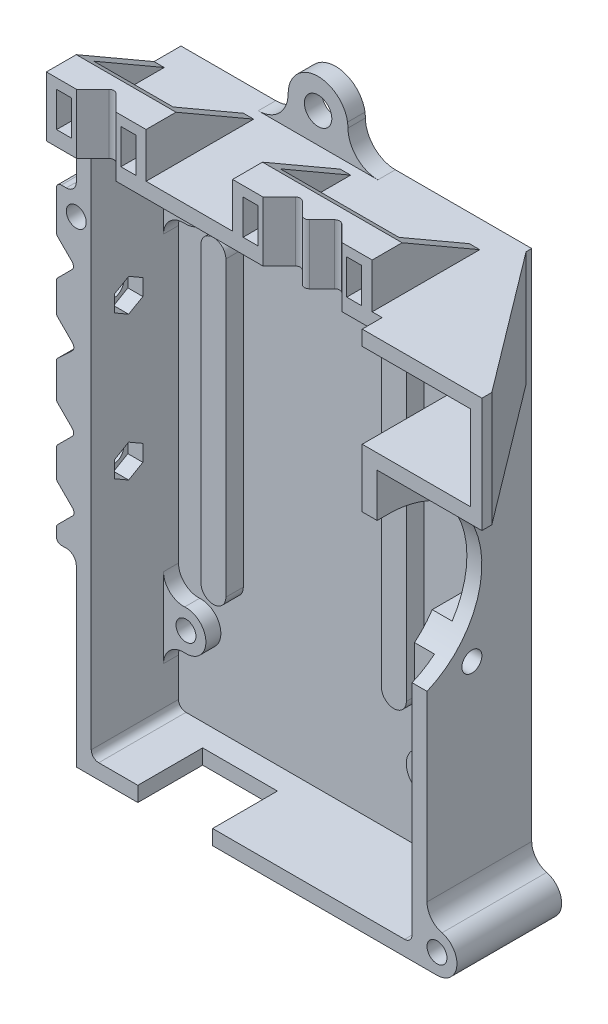
SolidWorks part; units mm, degrees
note: The reader was unsure of these and kept them because the rebuilt part matched: shared geometry of "Sketch6<4>", "Sketch11<3>", "Sketch11<4>".
ref_plane "Front Plane" through (0, 0, 0) normal (0, 0, 1) x (1, 0, 0)
ref_plane "Top Plane" through (0, 0, 0) normal (0, 1, 0) x (1, 0, 0)
ref_plane "Right Plane" through (0, 0, 0) normal (1, 0, 0) x (0, 0, -1)
sketch "Sketch6" plane through (0, 0, 0) normal (0, 0, 1) x (1, 0, 0)
  line L0 (4, 12) -> (4, 126.75)
  line L1 (4, 69.375) -> (74.35, 69.375) construction
  line L2 (74.35, 126.75) -> (4, 126.75)
  line L3 (23, 12) -> (47.3, 12)
  line L4 (74.35, 23.746) -> (74.35, 126.75)
  line L5 (71.35, 123.75) -> (7, 123.75)
  line L6 (69.85, 15) -> (8.5, 15)
  line L7 (71.35, 123.75) -> (71.35, 16.5)
  line L8 (76.35, 12) -> (47.3, 12)
  line L9 (7, 16.5) -> (7, 123.75)
  line L10 (23, 12) -> (4, 12)
  arc A3 (74.35, 23.746) -> (77.35, 19.873) centre (78.35, 23.746) ccw
  arc A4 (77.35, 19.873) -> (76.35, 12) centre (76.35, 16) cw
  arc A5 (23, 12) -> (29, 6) centre (23, 6) cw
  arc A6 (47.3, 12) -> (41, 5.998) centre (47.0109, 5.996) ccw
  arc A7 (41, 5.998) -> (29, 6) centre (35, 6) cw
  arc A8 (7, 16.5) -> (8.5, 15) centre (8.5, 16.5) ccw
  arc A9 (69.85, 15) -> (71.35, 16.5) centre (69.85, 16.5) ccw
  point P31 (0, 0)
  dimension "D1" = 4
  dimension "D2" = 4
  dimension "D3" = 6
  dimension "D4" = 6.0109
  dimension "D5" = 1.5
  dimension "D6" = 4
  dimension "D7" = 7
  dimension "D8" = 29
  dimension "D9" = 47.3
  dimension "D10" = 74.35
  dimension "D11" = 76.35
  dimension "D12" = 5.996
  dimension "D13" = 71.35
  dimension "D16" = 15
  dimension "D20" = 123.75
  dimension "D21" = 126.75
extrude "Boss-Extrude1" add sketch "Sketch6" along normal blind 21
extrude "Boss-Extrude2" add sketch "Sketch6<4>" along normal blind 3.5
sketch "Sketch6<4>" plane through (0, 0, 0) normal (0, 0, 1) x (1, 0, 0) same geometry as "Sketch6"
sketch "Sketch9" plane through (0, 0, 0) normal (0, 0, 1) x (1, 0, 0)
  line L0 (4, 12) -> (4, 126.75) construction
  line L1 (1, 111.5979) -> (2, 111.5979)
  line L2 (0, 103.0122) -> (0, 110.5979)
  line L3 (3.1815, 99.3365) -> (0.1809, 102.3372)
  line L4 (0, 89.1126) -> (0, 94.2842)
  line L5 (0.1809, 95.0234) -> (3.1815, 98.024)
  line L6 (0.1809, 88.3736) -> (3.1815, 85.373)
  line L7 (0.1809, 81.0599) -> (3.1815, 83.8996)
  line L8 (0, 74.2132) -> (0, 80.3848)
  line L9 (0.1809, 73.449) -> (3.1815, 70.4484)
  line L10 (4, 47) -> (4, 113.5979)
  line L11 (3.1815, 69.0344) -> (0.2832, 66.136)
  line L12 (0, 65.4853) -> (0, 60.3137)
  line L13 (3.1815, 56.7082) -> (0.2832, 59.6066)
  line L14 (3.1815, 55.1815) -> (0.2859, 52.2858)
  line L15 (0, 50) -> (0, 51.5858)
  line L16 (1, 49) -> (2, 49)
  line L18 (4, 12) -> (4, 47) construction
  arc A0 (4, 113.5979) -> (2, 111.5979) centre (2, 113.5979) cw
  arc A1 (1, 111.5979) -> (0, 110.5979) centre (1, 110.5979) ccw
  arc A2 (3.1815, 99.3365) -> (3.1815, 98.024) centre (2.427, 98.6803) cw
  arc A3 (0, 103.0122) -> (0.1809, 102.3372) centre (0.9955, 102.9172) ccw
  arc A4 (0, 94.2842) -> (0.1809, 95.0234) centre (0.9887, 94.4339) cw
  arc A5 (0, 89.1126) -> (0.1809, 88.3736) centre (0.9887, 88.963) ccw
  arc A6 (3.1815, 85.373) -> (3.1815, 83.8996) centre (2.5053, 84.6363) cw
  arc A7 (0, 80.3848) -> (0.1809, 81.0599) centre (0.9955, 80.4798) cw
  arc A8 (0, 74.2132) -> (0.1809, 73.449) centre (0.9854, 74.043) ccw
  arc A9 (3.1815, 69.0344) -> (3.1815, 70.4484) centre (2.4743, 69.7414) ccw
  arc A10 (0.2832, 66.136) -> (0, 65.4853) centre (0.9989, 65.4376) ccw
  arc A11 (0, 60.3137) -> (0.2832, 59.6066) centre (1, 60.3039) ccw
  arc A12 (3.1815, 56.7082) -> (3.1815, 55.1815) centre (2.5356, 55.9449) cw
  arc A13 (0.2859, 52.2858) -> (0, 51.5858) centre (1, 51.5858) ccw
  arc A14 (0, 50) -> (1, 49) centre (1, 50) ccw
  arc A15 (2, 49) -> (4, 47) centre (2, 47) cw
  point P1 (3.5356, 55.9449)
  point P39 (3.4743, 69.7414)
  point P57 (3.5053, 84.6363)
  point P58 (0, 0)
  point P60 (3.427, 98.6803)
  dimension "D1" = 2
  dimension "D2" = 1
  dimension "D3" = 1
  dimension "D4" = 1
  dimension "D5" = 1
  dimension "D6" = 1
  dimension "D7" = 1
  dimension "D8" = 1
  dimension "D9" = 1
  dimension "D10" = 1
  dimension "D11" = 1
  dimension "D12" = 1
  dimension "D13" = 1
  dimension "D14" = 1
  dimension "D15" = 1
  dimension "D16" = 2
  dimension "D17" = 1.5858
  dimension "D18" = 1
  dimension "D19" = 5.1716
  dimension "D20" = 7.3137
  dimension "D21" = 6.1716
  dimension "D22" = 7.3137
  dimension "D23" = 5.1716
  dimension "D24" = 7.3138
  dimension "D25" = 7.5858
  dimension "D26" = 1
  dimension "D27" = 4
  dimension "D28" = 35
  dimension "D29" = 2
  dimension "D30" = 135
  dimension "D31" = 135
  dimension "D32" = 90
  dimension "D33" = 90
  dimension "D34" = 3
  dimension "D35" = 1
  dimension "D36" = 0.7
  dimension "D37" = 7.3208
  dimension "D38" = 90
  dimension "D39" = 0.4644
  dimension "D40" = 0.2859
  dimension "D41" = 90
  dimension "D42" = 0.7392
  dimension "D43" = 135
  dimension "D44" = 135
  dimension "D45" = 1.5268
  dimension "D46" = 1.414
  dimension "D47" = 1.4733
  dimension "D48" = 0.7071
  dimension "D49" = 0.6507
  dimension "D50" = 0.7642
  dimension "D51" = 0.6751
  dimension "D52" = 0.7391
  dimension "D53" = 0.675
  dimension "D54" = 1
  dimension "D55" = 2
  dimension "D56" = 15.1521
  dimension "D57" = 13.1521
extrude "Boss-Extrude3" add sketch "Sketch9" along normal up to surface (21 mm away) up to face at (39.175, 51.6464, 21)
sketch "Sketch10" plane through (0, 0, 0) normal (0, 0, 1) x (1, 0, 0)
  circle A0 centre (35, 6) radius 2.75
  circle A1 centre (59.7, 31.2) radius 2
  circle A2 centre (76.35, 16) radius 2
  circle A3 centre (11.5, 32.2) radius 2
  circle A4 centre (4, 107.598) radius 2
  circle A5 centre (11.5, 106.8) radius 2
  circle A6 centre (35, 132.75) radius 2.75
  circle A7 centre (59.7, 113.9) radius 2
  point P15 (0, 0)
  dimension "D1" = 5.5
  dimension "D2" = 4
  dimension "D3" = 4
  dimension "D4" = 11.5
  dimension "D5" = 35
  dimension "D6" = 59.7
  dimension "D7" = 76.35
  dimension "D8" = 6
  dimension "D9" = 16
  dimension "D10" = 31.2
  dimension "D11" = 32.2
  dimension "D12" = 106.8
  dimension "D13" = 107.598
  dimension "D14" = 113.9
  dimension "D15" = 132.75
extrude "Cut-Extrude1" cut sketch "Sketch10" against normal through all both and the other way through all
sketch "Sketch11" plane through (0, 0, 0) normal (0, 0, 1) x (1, 0, 0)
  line L0 (20, 101.25) -> (20, 42.5)
  line L1 (15, 101.25) -> (15, 42.5)
  line L2 (56.2, 42.5) -> (56.2, 101.25)
  line L3 (51.2, 101.25) -> (51.2, 42.5)
  line L4 (7, 40.1844) -> (7, 24.2156)
  line L5 (71.35, 99) -> (71.35, 55)
  line L6 (7, 114.7844) -> (7, 98.8156)
  line L7 (67.35, 99) -> (71.35, 99)
  line L8 (67.35, 99) -> (67.35, 87)
  line L9 (67.35, 87) -> (71.35, 87)
  line L10 (7, 24.2156) -> (7, 40.1844) construction
  line L11 (71.35, 99) -> (71.35, 87)
  line L12 (67.35, 55) -> (71.35, 55)
  line L13 (67.35, 55) -> (67.35, 67)
  line L14 (67.35, 67) -> (71.35, 67)
  line L15 (71.35, 55) -> (71.35, 67)
  arc A0 (7, 114.7844) -> (11.25, 110.7922) centre (11, 114.7844) ccw
  arc A1 (11.25, 110.7922) -> (11.25, 102.8078) centre (11.5, 106.8) cw
  arc A2 (7, 40.1844) -> (11.25, 36.1922) centre (11, 40.1844) ccw
  arc A3 (11.25, 36.1922) -> (11.25, 28.2078) centre (11.5, 32.2) cw
  arc A4 (20, 42.5) -> (15, 42.5) centre (17.5, 42.5) cw
  arc A5 (51.2, 42.5) -> (56.2, 42.5) centre (53.7, 42.5) ccw
  arc A6 (7, 24.2156) -> (11.25, 28.2078) centre (11, 24.2156) cw
  circle A7 centre (59.7, 31.2) radius 4
  arc A8 (15, 101.25) -> (20, 101.25) centre (17.5, 101.25) cw
  arc A9 (51.2, 101.25) -> (56.2, 101.25) centre (53.7, 101.25) cw
  circle A10 centre (59.7, 113.9) radius 4
  arc A11 (7, 98.8156) -> (11.25, 102.8078) centre (11, 98.8156) cw
  point P10 (0, 0)
  point P39 (0, 0)
  dimension "D1" = 4
  dimension "D2" = 7
  dimension "D3" = 2.5
  dimension "D15" = 42.5
  dimension "D4" = 11.25
  dimension "D5" = 67.35
  dimension "D6" = 24.2156
  dimension "D7" = 55
  dimension "D8" = 53.7
  dimension "D9" = 59.7
  dimension "D10" = 31.2
  dimension "D11" = 67
  dimension "D12" = 87
  dimension "D13" = 98.8156
  dimension "D14" = 101.25
  dimension "D24" = 113.9
extrude "Boss-Extrude4" add sketch "Sketch11" along normal blind 7 contours L1 A4 L0 A8 | L3 A5 L2 A9
ref_plane "Plane1" through (0, 0, 1.1321) normal (0, 0, 1) x (1, 0, 0)
sketch "Sketch12" plane through (0, 0, 1.1321) normal (0, 0, 1) x (1, 0, 0)
  line L0 (74.35, 103.75) -> (95.35, 103.75)
  line L1 (95.35, 103.75) -> (95.35, 126.75)
  line L2 (95.35, 126.75) -> (71.35, 126.75)
  line L3 (71.35, 106.75) -> (93.1007, 106.75)
  line L4 (93.1007, 106.75) -> (93.1007, 123.75)
  line L5 (93.1007, 123.75) -> (71.35, 123.75)
  line L6 (71.35, 126.75) -> (71.35, 123.75)
  line L7 (71.35, 95) -> (74.35, 95)
  line L8 (74.35, 95) -> (74.35, 103.75)
  line L9 (71.35, 95) -> (71.35, 106.75)
  line L10 (72.378, 123.75) -> (72.378, 106.75)
  point P12 (0, 0)
  dimension "D1" = 71.35
  dimension "D2" = 72.378
  dimension "D3" = 74.35
  dimension "D4" = 93.1007
  dimension "D5" = 95.35
  dimension "D6" = 95
  dimension "D7" = 103.75
  dimension "D8" = 106.75
  dimension "D9" = 123.75
  dimension "D10" = 126.75
extrude "Boss-Extrude5" add sketch "Sketch12" along normal blind 29.8679 contours L9 L7 L8 L0 L1 L2 L6 L5 L4 L3 | L5 L10 L3 L4
extrude "Boss-Extrude7" add sketch "Sketch11<3>" along normal blind 16.5 contours L7 L8 L9 L11 | L12 L13 L14 L15
sketch "Sketch11<3>" plane through (0, 0, 0) normal (0, 0, 1) x (1, 0, 0) same geometry as "Sketch11"
sketch "Sketch15" plane through (0, 0, 31) normal (0, 0, 1) x (1, 0, 0)
  line L0 (93.1007, 106.75) -> (93.1007, 123.75) construction
  line L1 (93.1007, 123.75) -> (71.35, 123.75) construction
  line L2 (71.35, 106.75) -> (93.1007, 106.75) construction
  line L3 (71.35, 123.75) -> (71.35, 99) construction
  line L4 (93.1007, 106.75) -> (93.1007, 123.75)
  line L5 (93.1007, 123.75) -> (71.35, 123.75)
  line L6 (71.35, 106.75) -> (93.1007, 106.75)
  line L7 (71.35, 123.75) -> (71.35, 106.75)
sketch "Sketch16" plane through (0, 0, 3.5) normal (0, 0, 1) x (1, 0, 0)
  line L0 (72.378, 123.75) -> (72.378, 106.75) construction
  line L1 (72.378, 123.75) -> (72.378, 106.75)
  line L2 (72.378, 106.75) -> (67.378, 106.75)
  line L3 (67.378, 106.75) -> (67.378, 123.75)
  line L4 (67.378, 123.75) -> (72.378, 123.75)
  dimension "D1" = 5
ref_plane "Plane3" through (44.4818, 0, -33.5194) normal (-0.7986, 0, 0.6018) x (0.6018, 0, 0.7986)
sketch "Sketch17" plane through (44.4818, 0, -33.5194) normal (-0.7986, 0, 0.6018) x (0.6018, 0, 0.7986)
  line L0 (80.7871, 123.75) -> (67.6972, 123.75) construction
  line L1 (80.7871, 106.75) -> (80.7871, 123.75) construction
  line L2 (67.6972, 106.75) -> (80.7871, 106.75) construction
  line L4 (68.3158, 106.75) -> (60.3295, 106.75) construction
  line L5 (68.3158, 123.75) -> (60.3295, 123.75) construction
  line L6 (80.7871, 123.75) -> (67.6972, 123.75)
  line L7 (80.7871, 106.75) -> (80.7871, 123.75)
  line L8 (67.6972, 106.75) -> (80.7871, 106.75)
  line L9 (44.4622, 106.75) -> (44.4622, 123.75)
  line L10 (68.3158, 106.75) -> (44.4622, 106.75)
  line L11 (68.3158, 123.75) -> (44.4622, 123.75)
  line L15 (44.4622, 123.75) -> (44.4622, 106.75) construction
extrude "Cut-Extrude2" cut sketch "Sketch17" along normal through all contours L6 L11 L9 L10 L8 L7
extrude "Boss-Extrude9" add sketch "Sketch16" against normal up to surface (3.5 mm away) up to face at (11.784, 67.3273, 0)
sketch "Sketch18" plane through (0, 126.75, 0) normal (0, 1, 0) x (1, 0, 0)
  line L0 (95.35, -29) -> (74.35, -1.1321)
  line L1 (95.35, -31) -> (95.35, -1.1321) construction
  line L2 (74.35, -1.1321) -> (95.35, -1.1321)
  line L3 (95.35, -1.1321) -> (95.35, -29)
  dimension "D1" = 2
extrude "Cut-Extrude3" cut sketch "Sketch18" against normal up to next
extrude "Boss-Extrude10" add sketch "Sketch11<4>" along normal blind 6.5 contours L4 A6 A3 A2 | A7 | A10 | L6 A11 A1 A0
sketch "Sketch11<4>" plane through (0, 0, 0) normal (0, 0, 1) x (1, 0, 0) same geometry as "Sketch11"
sketch "Sketch20" plane through (0, 0, 3.5) normal (0, 0, 1) x (1, 0, 0)
  circle A3 centre (11.5, 106.8) radius 2
  circle A4 centre (11.5, 106.8) radius 2
  circle A7 centre (11.5, 32.2) radius 2
  circle A8 centre (11.5, 32.2) radius 2
  circle A11 centre (59.7, 31.2) radius 2
  circle A12 centre (59.7, 31.2) radius 2
  circle A15 centre (59.7, 113.9) radius 2
  circle A16 centre (59.7, 113.9) radius 2
  dimension "D2" = 0
  dimension "D4" = 0
  dimension "D6" = 0
  dimension "D8" = 0
extrude "Cut-Extrude5" cut sketch "Sketch20" against normal through all both and the other way through all
sketch "Sketch22" plane through (0, 0, 0) normal (1, 0, 0) x (0, 0, -1)
  line L0 (-21, 23.6548) -> (-21, 60.3257)
  line L1 (-31, 94.9088) -> (-31, 23.6548)
  line L2 (-31, 23.6548) -> (-21, 23.6548)
  arc A0 (-21, 60.3257) -> (-20.5489, 93.2217) centre (-27.9427, 76.872) ccw
  arc A1 (-20.5489, 93.2217) -> (-31, 94.9088) centre (-28.8873, 74.7832) ccw
  point P6 (0, 0)
  dimension "D1" = 17.9438
  dimension "D2" = 20.2362
  dimension "D3" = 20.5489
  dimension "D4" = 21
  dimension "D5" = 27.9427
  dimension "D6" = 23.6548
  dimension "D7" = 31
  dimension "D8" = 60.3257
sketch "Sketch23" plane through (74.35, 0, 0) normal (1, 0, 0) x (0, 0, -1)
  line L0 (-31, 94.9088) -> (-31, 23.6548) construction
  line L1 (-21, 23.6548) -> (-21, 60.3257) construction
  line L2 (-31, 23.6548) -> (-21, 23.6548) construction
  line L3 (-31, 94.9088) -> (-31, 23.6548)
  line L4 (-21, 23.6548) -> (-21, 60.3257)
  line L5 (-31, 23.6548) -> (-21, 23.6548)
  arc A0 (-20.5489, 93.2217) -> (-31, 94.9088) centre (-28.8873, 74.7832) ccw construction
  arc A1 (-21, 60.3257) -> (-20.5489, 93.2217) centre (-27.9427, 76.872) ccw construction
  arc A2 (-20.5489, 93.2217) -> (-31, 94.9088) centre (-28.8873, 74.7832) ccw
  arc A3 (-21, 60.3257) -> (-20.5489, 93.2217) centre (-27.9427, 76.872) ccw
extrude "Cut-Extrude6" cut sketch "Sketch23" against normal up to next
sketch "Sketch25" plane through (74.35, 0, 0) normal (1, 0, 0) x (0, 0, -1)
  line L0 (-21, 93.4191) -> (-21, 95)
  line L1 (-21, 95) -> (-28.0006, 95)
  arc A0 (-20.5489, 93.2217) -> (-31, 94.9088) centre (-28.8873, 74.7832) ccw construction
  arc A1 (-21, 93.4191) -> (-31, 94.9088) centre (-28.8873, 74.7832) ccw
  line M3 (-28.0006, 95) -> (-21, 95)
  line M4 (-21, 95) -> (-21, 93.4191)
extrude "Boss-Extrude12" add sketch "Sketch25" against normal up to surface (3 mm away) contours A1 M4 M3 up to face at (71.35, 97.181, 20.2035)
sketch "Sketch26" plane through (0, 0, 0) normal (1, 0, 0) x (0, 0, -1)
  circle A0 centre (-12, 61) radius 2
  circle A1 centre (-12, 93) radius 2
  point P0 (0, 0)
  dimension "D1" = 4
  dimension "D2" = 12
  dimension "D3" = 61
  dimension "D4" = 93
sketch "Sketch27" plane through (74.35, 0, 0) normal (1, 0, 0) x (0, 0, -1)
  circle A1 centre (-12, 93) radius 2
  circle A2 centre (-12, 93) radius 2
  circle A3 centre (-12, 61) radius 2
  circle A4 centre (-12, 61) radius 2
  dimension "D1" = 0
  dimension "D2" = 0
extrude "Cut-Extrude7" cut sketch "Sketch27" against normal up to next
sketch "Sketch29" plane through (0, 12, 0) normal (0, -1, 0) x (1, 0, 0)
  line L0 (16.3428, 21) -> (31.3428, 21)
  line L1 (16.3428, 21) -> (16.3428, 8)
  line L2 (16.3428, 8) -> (31.3428, 8)
  line L3 (31.3428, 21) -> (31.3428, 8)
  line L4 (46.7219, 21) -> (46.7219, 3.5) construction
  line L5 (23, 3.5) -> (46.7219, 3.5) construction
  point P4 (0, 0)
  dimension "D1" = 15.3791
  dimension "D2" = 30.3791
  dimension "D3" = 46.7219
  dimension "D4" = 4.5
  dimension "D5" = 17.5
  dimension "D6" = 3.5
extrude "Cut-Extrude8" cut sketch "Sketch29" against normal up to next
sketch "Sketch32" plane through (0, 0, 0) normal (0, 0, -1) x (-1, 0, 0)
  line L0 (-11.5, 28.9091) -> (-8.65, 30.5546)
  line L1 (-8.65, 30.5546) -> (-8.65, 33.8454)
  line L2 (-8.65, 33.8454) -> (-11.5, 35.4909)
  line L3 (-11.5, 35.4909) -> (-14.35, 33.8454)
  line L4 (-14.35, 33.8454) -> (-14.35, 30.5546)
  line L5 (-14.35, 30.5546) -> (-11.5, 28.9091)
  line L6 (0, 80.3848) -> (0, 74.2132) construction
  line L7 (-1, 49) -> (-2, 49) construction
  line L8 (-59.7, 27.9091) -> (-56.85, 29.5546)
  line L9 (-56.85, 29.5546) -> (-56.85, 32.8454)
  line L10 (-56.85, 32.8454) -> (-59.7, 34.4909)
  line L11 (-59.7, 34.4909) -> (-62.55, 32.8454)
  line L12 (-62.55, 32.8454) -> (-62.55, 29.5546)
  line L13 (-62.55, 29.5546) -> (-59.7, 27.9091)
  line L14 (-59.7, 110.6091) -> (-56.85, 112.2545)
  line L15 (-56.85, 112.2545) -> (-56.85, 115.5454)
  line L16 (-56.85, 115.5454) -> (-59.7, 117.1909)
  line L17 (-59.7, 117.1909) -> (-62.55, 115.5454)
  line L18 (-62.55, 115.5454) -> (-62.55, 112.2545)
  line L19 (-62.55, 112.2545) -> (-59.7, 110.6091)
  line L20 (-11.5, 103.5091) -> (-8.65, 105.1545)
  line L21 (-8.65, 105.1545) -> (-8.65, 108.4454)
  line L22 (-8.65, 108.4454) -> (-11.5, 110.0909)
  line L23 (-11.5, 110.0909) -> (-14.35, 108.4454)
  line L24 (-14.35, 108.4454) -> (-14.35, 105.1545)
  line L25 (-14.35, 105.1545) -> (-11.5, 103.5091)
  line L26 (-4, 12) -> (-4, 47) construction
  circle A0 centre (-11.5, 32.2) radius 2
  circle A1 centre (-11.5, 32.2) radius 2.85 construction
  circle A2 centre (-59.7, 31.2) radius 2
  circle A3 centre (-11.5, 32.2) radius 2 construction
  circle A4 centre (-11.5, 32.2) radius 2
  circle A5 centre (-59.7, 31.2) radius 2.85 construction
  circle A6 centre (-59.7, 31.2) radius 2
  circle A7 centre (-59.7, 113.9) radius 2
  circle A8 centre (-59.7, 113.9) radius 2.85 construction
  circle A9 centre (-59.7, 113.9) radius 2
  circle A10 centre (-11.5, 106.8) radius 2
  circle A11 centre (-11.5, 106.8) radius 2.85 construction
  circle A12 centre (-11.5, 106.8) radius 2
  circle A13 centre (-59.7, 113.9) radius 2 construction
  circle A14 centre (-11.5, 106.8) radius 2 construction
  circle A15 centre (-59.7, 31.2) radius 2 construction
  dimension "D1" = 5.7
  dimension "D2" = 5.7
  dimension "D3" = 5.7
  dimension "D4" = 5.7
  dimension "D5" = 4
  dimension "D8" = 4
  dimension "D11" = 4
  dimension "D14" = 4
  dimension "D6" = 3
  dimension "D7" = 2
  dimension "D9" = 3
  dimension "D10" = 2
  dimension "D12" = 3
  dimension "D13" = 2
extrude "Cut-Extrude10" cut sketch "Sketch32" against normal blind 3 contours L4 L5 L0 L1 L2 L3 A0 | L12 L13 L8 L9 L10 L11 A2 | L18 L19 L14 L15 L16 L17 A7 | L24 L25 L20 L21 L22 L23 A10
sketch "Sketch34" plane through (0, 0, 0) normal (0, 0, -1) x (-1, 0, 0)
  line L0 (0, 65.4853) -> (0, 60.3137) construction
  line L28 (-41, 132.75) -> (-40.9182, 133.7376)
  line L38 (-47, 126.75) -> (-47.3, 126.75)
  line L39 (-23, 126.75) -> (-47.3, 126.75)
  line L40 (-62.55, 115.5454) -> (-62.55, 112.2545) construction
  line L41 (-1, 49) -> (-2, 49) construction
  arc A0 (-29, 132.7388) -> (-23, 126.75) centre (-23, 132.75) ccw
  arc A1 (-29, 132.7388) -> (-40.9182, 133.7376) centre (-35.0019, 132.7276) ccw
  arc A2 (-47, 126.75) -> (-41, 132.75) centre (-47, 132.75) ccw
  circle A3 centre (-35, 132.75) radius 2.75
  point P7 (0, 0)
  point P44 (0, 0)
  dimension "D6" = 6
  dimension "D7" = 6.0019
  dimension "D12" = 5.5
  dimension "D18" = 62.55
  dimension "D1" = 15.25
  dimension "D2" = 39.55
  dimension "D3" = 61.55
  dimension "D4" = 66.5455
  dimension "D5" = 77.75
  dimension "D8" = 29
  dimension "D9" = 49
  dimension "D10" = 40.9182
  dimension "D11" = 41
  dimension "D13" = 27.55
  dimension "D14" = 61.55
  dimension "D15" = 66.5455
  dimension "D16" = 1
  dimension "D17" = 16.4853
extrude "Boss-Extrude13" add sketch "Sketch34" against normal blind 3.5 contours A2 L39 A0 A1 L28 A3
ref_plane "Plane2" through (0, 0, 5.4115) normal (0, 0, 1) x (1, 0, 0)
sketch "Sketch36" plane through (0, 0, 5.4115) normal (0, 0, 1) x (1, 0, 0)
  line L0 (41.35, 135.75) -> (69.35, 135.75)
  line L1 (74.35, 126.75) -> (47, 126.75) construction
  line L2 (4, 113.5979) -> (4, 126.75) construction
  line L3 (69.35, 135.75) -> (69.35, 126.75)
  line L4 (4, 135.75) -> (24, 135.75)
  line L5 (4, 135.75) -> (4, 123.75)
  line L6 (71.35, 123.75) -> (4, 123.75)
  line L7 (41.35, 126.75) -> (41.35, 135.75)
  line L8 (67.2495, 133.75) -> (64.2495, 133.75)
  line L9 (67.2495, 133.75) -> (67.2495, 126.75)
  line L10 (67.2495, 126.75) -> (64.2495, 126.75)
  line L11 (64.2495, 133.75) -> (64.2495, 126.75)
  line L12 (46.4505, 133.75) -> (43.4505, 133.75)
  line L13 (46.4505, 133.75) -> (46.4505, 126.75)
  line L14 (46.4505, 126.75) -> (43.4505, 126.75)
  line L15 (43.4505, 133.75) -> (43.4505, 126.75)
  line L16 (21.9497, 133.75) -> (18.9497, 133.75)
  line L17 (21.9497, 133.75) -> (21.9497, 126.75)
  line L18 (21.9497, 126.75) -> (18.9497, 126.75)
  line L19 (18.9497, 133.75) -> (18.9497, 126.75)
  line L20 (9.0503, 133.75) -> (6.0503, 133.75)
  line L21 (9.0503, 133.75) -> (9.0503, 126.75)
  line L22 (9.0503, 126.75) -> (6.0503, 126.75)
  line L23 (6.0503, 133.75) -> (6.0503, 126.75)
  line L24 (71.35, 126.75) -> (71.35, 123.75)
  line L25 (71.35, 126.75) -> (69.35, 126.75)
  line L26 (71.35, 126.75) -> (4, 126.75) construction
  line L27 (41.35, 126.75) -> (24, 126.75)
  line L28 (24, 126.75) -> (24, 135.75)
  dimension "D1" = 2.0503
  dimension "D2" = 9.8995
  dimension "D3" = 20
  dimension "D4" = 9.0503
  dimension "D5" = 43.4505
  dimension "D6" = 17.799
  dimension "D7" = 28
  dimension "D8" = 133.75
  dimension "D9" = 41.35
  dimension "D10" = 135.75
extrude "Boss-Extrude15" add sketch "Sketch36" along normal blind 21.5885
sketch "Sketch38" plane through (0, 0, 5.4115) normal (0, 0, -1) x (-1, 0, 0)
  line L0 (-67.2495, 133.75) -> (-43.4505, 133.75)
  line L1 (-67.2495, 133.75) -> (-67.2495, 126.75)
  line L2 (-67.2495, 126.75) -> (-43.4505, 126.75)
  line L3 (-43.4505, 133.75) -> (-43.4505, 126.75)
  line L4 (-21.9497, 133.75) -> (-6.0502, 133.75)
  line L5 (-21.9497, 133.75) -> (-21.9497, 126.75)
  line L6 (-21.9497, 126.75) -> (-6.0502, 126.75)
  line L7 (-6.0502, 133.75) -> (-6.0502, 126.75)
  line L8 (-69.35, 126.75) -> (-69.35, 135.75) construction
  line L9 (-69.35, 126.75) -> (-67.2495, 126.75) construction
  point P8 (0, 0)
  dimension "D1" = 2.1005
  dimension "D2" = 25.8995
  dimension "D3" = 47.4003
  dimension "D4" = 63.2998
  dimension "D5" = 69.35
  dimension "D6" = 7
  dimension "D7" = 126.75
extrude "Cut-Extrude12" cut sketch "Sketch38" against normal blind 15.3244
sketch "Sketch39" plane through (69.35, 0, 0) normal (1, 0, 0) x (0, 0, -1)
  line L0 (-27, 135.75) -> (-27, 126.75)
  line L1 (-21, 135.75) -> (-27, 135.75)
  line L2 (-5.4115, 126.75) -> (-21, 135.75)
  line L3 (-5.4115, 126.75) -> (-27, 126.75)
  line L4 (-5.4115, 126.75) -> (-5.4115, 135.75) construction
  line L5 (-27, 135.75) -> (-5.4115, 135.75) construction
  line L6 (-27, 126.75) -> (-27, 135.75) construction
  line L7 (-1.1321, 126.75) -> (0, 126.75) construction
  line L8 (-5.4115, 126.75) -> (-5.4115, 135.75)
  line L9 (-5.4115, 135.75) -> (-21, 135.75)
  point P4 (0, 0)
  line M5 (-5.4115, 126.75) -> (-5.4115, 135.75)
  line M6 (-5.4115, 135.75) -> (-27, 135.75)
  dimension "D1" = 60
extrude "Cut-Extrude13" cut sketch "Sketch39" against normal through all contours L2 M5 M6
ref_plane "Plane4" through (0, 0, 19.5359) normal (0, 0, -1) x (-1, 0, 0)
sketch "Sketch40" plane through (0, 0, 19.5359) normal (0, 0, -1) x (-1, 0, 0)
  line L0 (-41.35, 135.75) -> (-69.35, 135.75) construction
  line L1 (-67.2495, 133.75) -> (-43.4505, 133.75)
  line L2 (-67.2495, 133.75) -> (-67.2495, 135.75)
  line L3 (-67.2495, 135.75) -> (-43.4505, 135.75)
  line L4 (-43.4505, 133.75) -> (-43.4505, 135.75)
  line L5 (-43.4505, 126.75) -> (-43.4505, 133.75) construction
  line L7 (-4, 135.75) -> (-24, 135.75) construction
  line L8 (-6.0503, 133.75) -> (-21.9497, 133.75) construction
  line L9 (-6.0503, 135.75) -> (-21.9497, 135.75)
  line L10 (-6.0503, 133.75) -> (-21.9497, 133.75)
  line L11 (-21.9497, 133.75) -> (-21.9497, 135.75)
  line L12 (-6.0503, 133.75) -> (-6.0503, 135.75)
extrude "Cut-Extrude14" cut sketch "Sketch40" along normal up to next
sketch "Sketch41" plane through (4, 0, 0) normal (-1, 0, 0) x (0, 0, 1)
  line L0 (21, 12) -> (21, 47) construction
  line L1 (21, 47) -> (0, 47) construction
  circle A0 centre (13.5, 91.6985) radius 2
  circle A1 centre (13.5, 62.8995) radius 2
  point P0 (0, 0)
  dimension "D1" = 4
  dimension "D2" = 7.5
  dimension "D3" = 21
  dimension "D4" = 15.8995
  dimension "D5" = 44.6985
  dimension "D6" = 47
extrude "Cut-Extrude16" cut sketch "Sketch41" against normal up to surface (3 mm away) and the other way through all up to face at (7, 69.7083, 7.4167)
sketch "Sketch42" plane through (0, 126.75, 0) normal (0, 1, 0) x (1, 0, 0)
  line L0 (10.0503, -27) -> (17.9497, -27)
  line L1 (10.0503, -27) -> (13.2929, -23.7574)
  line L2 (14.7071, -23.7574) -> (17.9497, -27)
  line L3 (63.2495, -27) -> (47.4505, -27)
  line L4 (69.35, -27) -> (41.35, -27) construction
  line L5 (47.4505, -27) -> (50.6931, -23.7574)
  line L6 (52.1073, -23.7574) -> (54.6429, -26.2929)
  line L7 (56.0571, -26.2929) -> (58.5926, -23.7574)
  line L8 (63.2495, -27) -> (60.0069, -23.7574)
  line L9 (24, -27) -> (4, -27) construction
  line L16 (6.0503, -27) -> (6.0503, -5.4115) construction
  arc A0 (56.0571, -26.2929) -> (54.6429, -26.2929) centre (55.35, -25.5858) cw
  arc A1 (60.0069, -23.7574) -> (58.5926, -23.7574) centre (59.2997, -24.4645) ccw
  arc A2 (52.1073, -23.7574) -> (50.6931, -23.7574) centre (51.4002, -24.4645) ccw
  arc A3 (14.7071, -23.7574) -> (13.2929, -23.7574) centre (14, -24.4645) ccw
  point P20 (0, 0)
  dimension "D1" = 1
  dimension "D2" = 4
  dimension "D3" = 7.2426
  dimension "D4" = 8.6569
  dimension "D5" = 41.4002
  dimension "D6" = 46.0571
  dimension "D7" = 48.5926
  dimension "D8" = 50.0068
  dimension "D9" = 53.9566
  dimension "D10" = 21.5885
extrude "Cut-Extrude17" cut sketch "Sketch42" against normal up to next and the other way up to next contours L6 A2 L5 L3 L8 A1 L7 A0 | L2 A3 L1 L0
sketch "Sketch43" plane through (67.35, 0, 0) normal (-1, 0, 0) x (0, 0, 1)
  line L0 (12, 57.7091) -> (14.85, 59.3546)
  line L1 (14.85, 59.3546) -> (14.85, 62.6454)
  line L2 (14.85, 62.6454) -> (12, 64.2909)
  line L3 (12, 64.2909) -> (9.15, 62.6454)
  line L4 (9.15, 62.6454) -> (9.15, 59.3546)
  line L5 (9.15, 59.3546) -> (12, 57.7091)
  line L6 (12, 89.7091) -> (14.85, 91.3546)
  line L7 (14.85, 91.3546) -> (14.85, 94.6454)
  line L8 (14.85, 94.6454) -> (12, 96.2909)
  line L9 (12, 96.2909) -> (9.15, 94.6454)
  line L10 (9.15, 94.6454) -> (9.15, 91.3546)
  line L11 (9.15, 91.3546) -> (12, 89.7091)
  circle A0 centre (12, 61) radius 2
  circle A1 centre (12, 61) radius 2.85 construction
  circle A2 centre (12, 61) radius 2
  circle A3 centre (12, 61) radius 2 construction
  circle A4 centre (12, 93) radius 2
  circle A5 centre (12, 93) radius 2.85 construction
  circle A6 centre (12, 93) radius 2
  circle A7 centre (12, 93) radius 2 construction
  circle M1 centre (12, 61) radius 2
  dimension "D1" = 5.7
  dimension "D2" = 4
  dimension "D3" = 5.7
  dimension "D4" = 4
extrude "Cut-Extrude18" cut sketch "Sketch43" against normal blind 3 contours L4 L5 L0 L1 L2 L3 M1 | L10 L11 L6 L7 L8 L9 A4
sketch "Sketch44" plane through (7, 0, 0) normal (1, 0, 0) x (0, 0, -1)
  line L0 (-13.5, 88.4076) -> (-10.65, 90.053)
  line L1 (-10.65, 90.053) -> (-10.65, 93.3439)
  line L2 (-10.65, 93.3439) -> (-13.5, 94.9894)
  line L3 (-13.5, 94.9894) -> (-16.35, 93.3439)
  line L4 (-16.35, 93.3439) -> (-16.35, 90.053)
  line L5 (-16.35, 90.053) -> (-13.5, 88.4076)
  line L6 (-13.5, 59.6086) -> (-10.65, 61.254)
  line L7 (-10.65, 61.254) -> (-10.65, 64.5449)
  line L8 (-10.65, 64.5449) -> (-13.5, 66.1904)
  line L9 (-13.5, 66.1904) -> (-16.35, 64.5449)
  line L10 (-16.35, 64.5449) -> (-16.35, 61.254)
  line L11 (-16.35, 61.254) -> (-13.5, 59.6086)
  circle A0 centre (-13.5, 91.6985) radius 2
  circle A1 centre (-13.5, 91.6985) radius 2.85 construction
  circle A2 centre (-13.5, 91.6985) radius 2
  circle A3 centre (-13.5, 62.8995) radius 2
  circle A4 centre (-13.5, 62.8995) radius 2.85 construction
  circle A5 centre (-13.5, 62.8995) radius 2
  circle A6 centre (-13.5, 62.8995) radius 2 construction
  circle A7 centre (-13.5, 91.6985) radius 2 construction
  circle M1 centre (-13.5, 62.8995) radius 2
  circle M2 centre (-13.5, 91.6985) radius 2
  dimension "D1" = 5.7
  dimension "D2" = 4
  dimension "D3" = 5.7
  dimension "D4" = 4
extrude "Cut-Extrude19" cut sketch "Sketch44" against normal blind 3 contours L10 L11 L6 L7 L8 L9 M1 | L4 L5 L0 L1 L2 L3 M2
